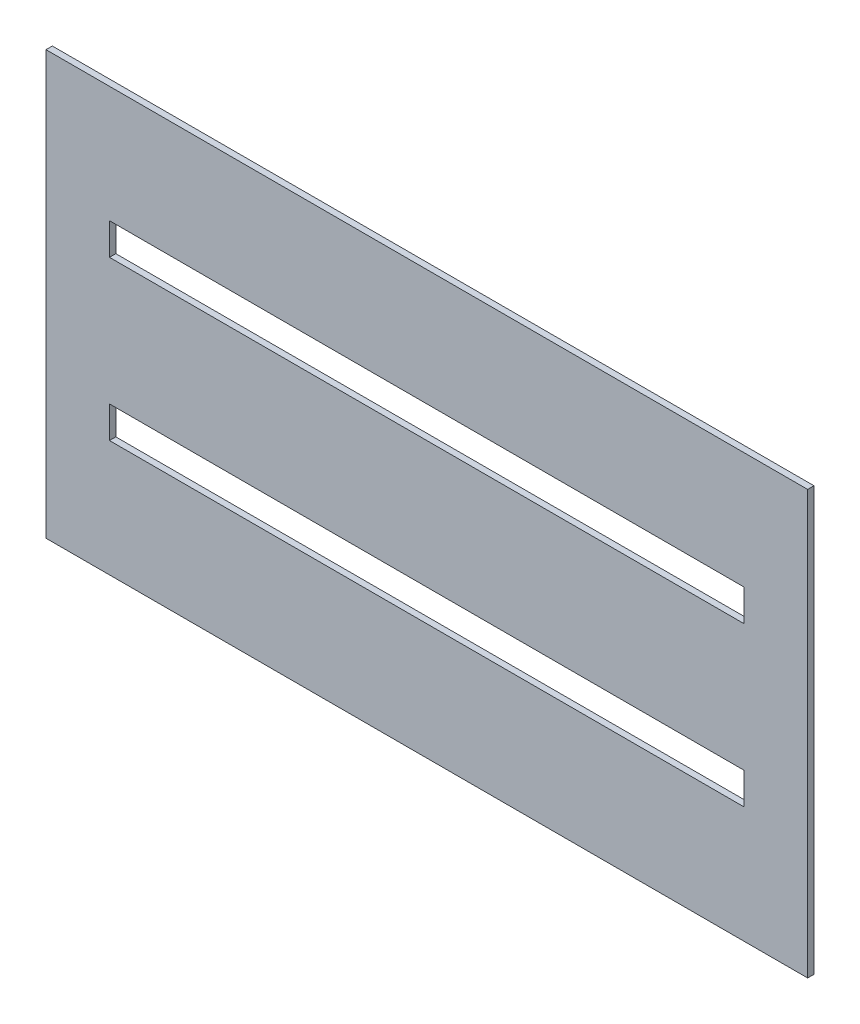
SolidWorks part; units mm, degrees
ref_plane "Alzado" through (0, 0, 0) normal (0, 0, 1) x (1, 0, 0)
ref_plane "Planta" through (0, 0, 0) normal (0, 1, 0) x (1, 0, 0)
ref_plane "Vista lateral" through (0, 0, 0) normal (1, 0, 0) x (0, 0, -1)
sketch "Croquis1" plane through (0, 0, 0) normal (0, 0, 1) x (1, 0, 0)
  line L1 (-180, 100) -> (180, 100)
  line L2 (-180, 100) -> (-180, -100)
  line L3 (-180, -100) -> (180, -100)
  line L4 (180, 100) -> (180, -100)
  line L5 (-180, 100) -> (180, -100) construction
  line L6 (-180, -100) -> (180, 100) construction
  point P0 (0, 0)
  dimension "D1" = 360
  dimension "D2" = 200
extrude "Saliente-Extruir1" add sketch "Croquis1" along normal blind 3
sketch "Croquis2" plane through (0, 0, 0) normal (0, 0, -1) x (-1, 0, 0)
  line L0 (0, 100) -> (0, -100) construction
  line L1 (-180, 100) -> (180, 100) construction
  line L2 (180, -100) -> (-180, -100) construction
  line L4 (150, 30) -> (-150, 30)
  line L5 (150, 30) -> (150, 45)
  line L6 (150, 45) -> (-150, 45)
  line L7 (-150, 30) -> (-150, 45)
  line L8 (150, 30) -> (-150, 45) construction
  line L9 (150, 45) -> (-150, 30) construction
  line L10 (-180, 0) -> (180, 0) construction
  line L11 (-180, -100) -> (-180, 100) construction
  line L12 (180, 100) -> (180, -100) construction
  line L13 (150, -30) -> (150, -45)
  line L14 (150, -30) -> (-150, -30)
  line L15 (-150, -30) -> (-150, -45)
  line L16 (150, -45) -> (-150, -45)
  point P6 (0, 37.5)
  dimension "D1" = 300
  dimension "D2" = 15
  dimension "D3" = 55
extrude "Cortar-Extruir1" cut sketch "Croquis2" against normal blind 10
equation "\"largo\"= 330mm"
equation "\"ancho\"= 200mm"
